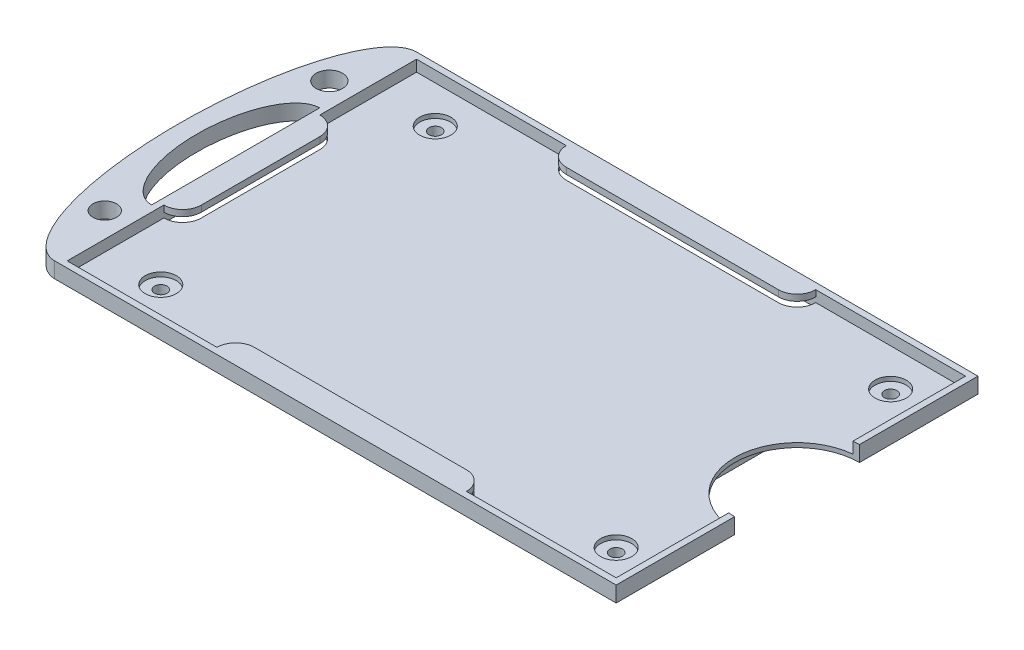
SolidWorks part; units mm, degrees
ref_plane "Front" through (0, 0, 0) normal (0, 0, 1) x (1, 0, 0)
ref_plane "Top" through (0, 0, 0) normal (0, 1, 0) x (1, 0, 0)
ref_plane "Right" through (0, 0, 0) normal (1, 0, 0) x (0, 0, -1)
sketch "Çizim1" plane through (0, 0, 0) normal (0, 1, 0) x (1, 0, 0)
  line L1 (-46.1164, 15.8979) -> (43.8836, 15.8979)
  line L2 (-46.1164, 15.8979) -> (-46.1164, -42.1021)
  line L3 (-46.1164, -42.1021) -> (43.8836, -42.1021)
  line L4 (43.8836, 15.8979) -> (43.8836, -42.1021)
  dimension "D1" = 90
  dimension "D2" = 58
extrude "Yükseklik-Ekstrüzyon1" add sketch "Çizim1" along normal blind 2.5 contours L4 L3 L2 L1
sketch "Çizim16" plane through (0, 2.5, 0) normal (0, 1, 0) x (1, 0, 0)
  line L11 (-45.1164, -41.1021) -> (42.8836, -41.1021)
  line L12 (42.8836, -41.1021) -> (42.8836, 14.8979)
  line L14 (42.8836, 14.8979) -> (-45.1164, 14.8979)
  line L17 (-45.1164, 14.8979) -> (-45.1164, -41.1021)
  line L22 (-45.1164, -41.1021) -> (42.8836, -41.1021)
  line L23 (42.8836, -41.1021) -> (42.8836, 14.8979)
  line L25 (42.8836, 14.8979) -> (-45.1164, 14.8979)
  line L28 (-45.1164, 14.8979) -> (-45.1164, -41.1021)
  dimension "D1" = 0
sketch "Çizim3" plane through (0, 2.5, 0) normal (0, 1, 0) x (1, 0, 0)
  line L0 (43.8836, 15.8979) -> (43.8836, -42.1021) construction
  circle A0 centre (43.8836, -13.1021) radius 10
  dimension "D1" = 20
extrude "Kes-Ekstrüzyon2" cut sketch "Çizim3" against normal blind 30.7
extrude "Kes-Ekstrüzyon9" cut sketch "Çizim16" against normal blind 1.8
sketch "Çizim4" plane through (0, 2.5, 0) normal (0, 1, 0) x (1, 0, 0)
  line L0 (-46.1164, 15.8979) -> (-46.1164, -42.1021) construction
  line L1 (-21.1164, 11.8979) -> (-21.1164, 15.8979)
  line L2 (-46.1164, 15.8979) -> (43.8836, 15.8979) construction
  line L3 (18.8836, 11.8979) -> (-21.1164, 11.8979)
  line L4 (18.8836, 11.8979) -> (18.8836, 15.8979)
  line L5 (-46.1164, -42.1021) -> (43.8836, -42.1021) construction
  line L6 (43.8836, 15.8979) -> (43.8836, -3.1021) construction
  line L8 (-21.1164, -42.1021) -> (18.8836, -42.1021)
  line L9 (18.8836, -38.1021) -> (18.8836, -42.1021)
  line L10 (18.8836, -38.1021) -> (-21.1164, -38.1021)
  line L11 (-21.1164, 15.8979) -> (18.8836, 15.8979)
  line L12 (-21.1164, -38.1021) -> (-21.1164, -42.1021)
  line L13 (43.8836, -23.1021) -> (43.8836, -42.1021) construction
  line L14 (-46.1164, -0.6021) -> (-42.1164, -0.6021)
  line L15 (-46.1164, -0.6021) -> (-46.1164, -25.6021)
  line L16 (-46.1164, -25.6021) -> (-42.1164, -25.6021)
  line L17 (-42.1164, -0.6021) -> (-42.1164, -25.6021)
  point P22 (-21.1164, -40.1021)
  dimension "D1" = 4
  dimension "D2" = 40
  dimension "D3" = 25
  dimension "D4" = 25
  dimension "D5" = 16.5
  dimension "D6" = 4
  dimension "D7" = 4
  dimension "D8" = 0
  dimension "D9" = 25
  dimension "D10" = 40
extrude "Yükseklik-Ekstrüzyon2" add sketch "Çizim4" against normal blind 1
fillet "Radyus1" radius 3 6 edges at (18.8836, 2, -11.8979) (-21.1164, 2, -11.8979) (-21.1164, 2, 38.1021) (18.8836, 2, 38.1021) (-42.1164, 2, 25.6021) (-42.1164, 2, 0.6021)
sketch "Çizim5" plane through (0, 1.5, 0) normal (0, -1, 0) x (-1, 0, 0)
  line L0 (21.1164, 14.8979) -> (-18.8836, 14.8979) construction
  line L1 (-15.8836, 11.8979) -> (18.1164, 11.8979) construction
  line L2 (-18.8836, -41.1021) -> (21.1164, -41.1021) construction
  line L3 (18.1164, -38.1021) -> (-15.8836, -38.1021) construction
  line L4 (21.1164, 14.8979) -> (-18.8836, 14.8979)
  line L5 (-15.8836, 11.8979) -> (18.1164, 11.8979)
  line L6 (-18.8836, -41.1021) -> (21.1164, -41.1021)
  line L7 (18.1164, -38.1021) -> (-15.8836, -38.1021)
  line L10 (42.1164, -3.6021) -> (42.1164, -22.6021)
  line L11 (45.1164, -25.6021) -> (45.1164, -0.6021)
  line L12 (42.1164, -3.6021) -> (42.1164, -22.6021)
  line L13 (45.1164, -25.6021) -> (45.1164, -0.6021)
  arc A0 (-18.8836, 14.8979) -> (-15.8836, 11.8979) centre (-15.8836, 14.8979) ccw construction
  arc A1 (18.1164, 11.8979) -> (21.1164, 14.8979) centre (18.1164, 14.8979) ccw construction
  arc A2 (21.1164, -41.1021) -> (18.1164, -38.1021) centre (18.1164, -41.1021) ccw construction
  arc A3 (-15.8836, -38.1021) -> (-18.8836, -41.1021) centre (-15.8836, -41.1021) ccw construction
  arc A4 (-18.8836, 14.8979) -> (-15.8836, 11.8979) centre (-15.8836, 14.8979) ccw
  arc A5 (18.1164, 11.8979) -> (21.1164, 14.8979) centre (18.1164, 14.8979) ccw
  arc A6 (21.1164, -41.1021) -> (18.1164, -38.1021) centre (18.1164, -41.1021) ccw
  arc A7 (-15.8836, -38.1021) -> (-18.8836, -41.1021) centre (-15.8836, -41.1021) ccw
  arc A10 (42.1164, -22.6021) -> (45.1164, -25.6021) centre (45.1164, -22.6021) ccw
  arc A11 (42.1164, -22.6021) -> (45.1164, -25.6021) centre (45.1164, -22.6021) ccw
  arc A12 (45.1164, -0.6021) -> (42.1164, -3.6021) centre (45.1164, -3.6021) ccw
  arc A13 (45.1164, -0.6021) -> (42.1164, -3.6021) centre (45.1164, -3.6021) ccw
  dimension "D1" = 0
extrude "Kes-Ekstrüzyon3" cut sketch "Çizim5" along normal blind 31
sketch "Çizim8" plane through (0, 0, 0) normal (0, -1, 0) x (1, 0, 0)
  line L0 (27.8836, 36.1021) -> (-27.1164, 36.1021)
  line L2 (-17.8779, 34.1021) -> (-25.1164, 34.1021)
  line L3 (14.3219, 34.1021) -> (25.8836, 34.1021)
  line L4 (-17.6164, -7.8979) -> (-25.1164, -7.8979)
  line L5 (14.3836, -7.8979) -> (25.8836, -7.8979)
  line L6 (-28.1164, 21.4029) -> (-28.1164, 31.1021)
  line L7 (-28.1164, 4.3697) -> (-28.1164, -4.8979)
  line L8 (-30.1164, 33.1021) -> (-30.1164, -6.8979)
  line L9 (-27.1164, -9.8979) -> (27.8836, -9.8979)
  line L10 (43.8836, 23.1021) -> (43.8836, 42.1021) construction
  line L11 (28.8836, 31.1021) -> (28.8836, -4.8979)
  line L12 (43.8836, 23.1021) -> (43.8836, 42.1021)
  line L13 (43.8836, 34.1021) -> (43.8836, 42.1021)
  line L14 (43.8836, 42.1021) -> (-46.1164, 42.1021)
  line L15 (43.8836, 42.1021) -> (-46.1164, 42.1021)
  line L16 (-46.1164, 42.1021) -> (-46.1164, -15.8979)
  line L17 (-46.1164, 42.1021) -> (-46.1164, -15.8979)
  line L18 (-46.1164, -15.8979) -> (43.8836, -15.8979)
  line L19 (-46.1164, -15.8979) -> (43.8836, -15.8979)
  line L20 (43.8836, -15.8979) -> (43.8836, 3.1021)
  line L22 (30.8836, 33.1021) -> (30.8836, -6.8979)
  line L37 (14.3219, 34.1021) -> (-17.8779, 34.1021)
  line L42 (-28.1164, 21.4029) -> (-28.1164, 4.3697)
  line L47 (-17.6164, -7.8979) -> (14.3836, -7.8979)
  arc A0 (-27.1164, 36.1021) -> (-30.1164, 33.1021) centre (-27.1164, 33.1021) ccw
  arc A1 (43.8836, 23.1021) -> (43.8836, 3.1021) centre (43.8836, 13.1021) ccw
  arc A2 (-28.1164, 31.1021) -> (-25.1164, 34.1021) centre (-25.1164, 31.1021) cw
  arc A3 (30.8836, 33.1021) -> (27.8836, 36.1021) centre (27.8836, 33.1021) ccw
  arc A4 (28.8836, 31.1021) -> (25.8836, 34.1021) centre (25.8836, 31.1021) ccw
  arc A5 (28.8836, -4.8979) -> (25.8836, -7.8979) centre (25.8836, -4.8979) cw
  arc A6 (30.8836, -6.8979) -> (27.8836, -9.8979) centre (27.8836, -6.8979) cw
  arc A7 (-28.1164, -4.8979) -> (-25.1164, -7.8979) centre (-25.1164, -4.8979) ccw
  arc A8 (-30.1164, -6.8979) -> (-27.1164, -9.8979) centre (-27.1164, -6.8979) ccw
  dimension "D6" = 6
  dimension "D8" = 16
  dimension "D10" = 3
  dimension "D2" = 0
  dimension "D3" = 2
  dimension "D4" = 2
  dimension "D5" = 2
  dimension "D7" = 6
  dimension "D9" = 2
  dimension "D11" = 2
  dimension "D12" = 61
extrude "Yükseklik-Ekstrüzyon5" add sketch "Çizim8" along normal blind 3.8 contours L47 L42 L37 region at (29.4647, 0, 34.6832)
sketch "Çizim7" plane through (0, 0, 0) normal (0, -1, 0) x (1, 0, 0)
  circle A0 centre (-7.9682, 1.249) radius 0.75
  circle A1 centre (-8.9182, 24.5434) radius 0.75
  point P4 (-2.4003, 0.9032)
  point P5 (-7.9682, 1.249)
  dimension "D1" = 1.5
  dimension "D2" = 1.5
  dimension "D3" = 0.95
  dimension "D4" = 23.2944
extrude "Yükseklik-Ekstrüzyon4" add sketch "Çizim7" along normal blind 3
sketch "Çizim12" plane through (0, 2.5, 0) normal (0, 1, 0) x (1, 0, 0)
  line L0 (-46.1164, 15.8979) -> (-46.1164, -42.1021) construction
  line L1 (-46.1164, -42.1021) -> (-46.1164, 15.8979)
  circle A0 centre (-49.0922, 4.8979) radius 2.1184
  circle A1 centre (-49.0922, -31.1021) radius 1.8932
  ellipse E0 centre (-46.1164, -13.1021) end of major axis (-46.1164, 0.362) minor radius 6.2149 (-46.1164, 0.362) -> (-46.1164, -26.5663) ccw
  ellipse E1 centre (-46.1164, -13.1021) end of major axis (-46.1164, 15.8979) minor radius 9.1098 (-46.1164, 15.8979) -> (-46.1164, -42.1021) ccw
  point P20 (-46.1164, -26.5663)
  line M15 (-46.1164, 15.8979) -> (-46.1164, -42.1021)
  dimension "D1" = 18
  dimension "D2" = 18
extrude "Yükseklik-Ekstrüzyon6" add sketch "Çizim12" against normal up to surface (2.5 mm away) contours E1 E0 M15 region at (-54.6391, 2.5, 13.1021) up to face at (0.3836, 0, 13.1021)
sketch "Çizim13" plane through (0, 0, 0) normal (0, -1, 0) x (-1, 0, 0)
  line L0 (46.1164, -42.1021) -> (-43.8836, -42.1021) construction
  line L1 (-43.8836, -23.1021) -> (-43.8836, -42.1021) construction
  line L2 (46.1164, 15.8979) -> (-43.8836, 15.8979) construction
  line L3 (-43.8836, 15.8979) -> (-43.8836, -3.1021) construction
  circle A0 centre (-36.8836, -35.1021) radius 4
  circle A1 centre (-36.8836, 8.8979) radius 4
  circle A2 centre (36.1164, -35.1021) radius 4
  circle A3 centre (36.1164, 8.8979) radius 4
  circle A4 centre (36.1164, -35.1021) radius 1
  circle A5 centre (36.1164, 8.8979) radius 1
  circle A6 centre (-36.8836, -35.1021) radius 1
  circle A7 centre (-36.8836, 8.8979) radius 1
  point P16 (36.1164, 8.8979)
  point P17 (36.1164, -35.1021)
  dimension "D2" = 73
  dimension "D8" = 8
  dimension "D11" = 2
  dimension "D3" = 7
  dimension "D4" = 7
  dimension "D5" = 7
  dimension "D6" = 7
extrude "Yükseklik-Ekstrüzyon7" add sketch "Çizim13" along normal blind 2 contours A2 A4 | A3 A5 | A1 A7 | A0 A6 region at (40.7705, 0, 35.1021) region at (40.7705, 0, -8.8979) region at (-32.2295, 0, 35.1021) region at (-32.2295, 0, -8.8979)
sketch "Çizim14" plane through (0, 1, 0) normal (0, 1, 0) x (1, 0, 0)
  circle A0 centre (-36.1164, -35.1021) radius 2.5
  circle A1 centre (-36.1164, 8.8979) radius 2.5
  circle A2 centre (36.8836, -35.1021) radius 2.5
  circle A3 centre (36.8836, 8.8979) radius 2.5
  dimension "D1" = 5
extrude "Kes-Ekstrüzyon5" cut sketch "Çizim14" against normal blind 1
